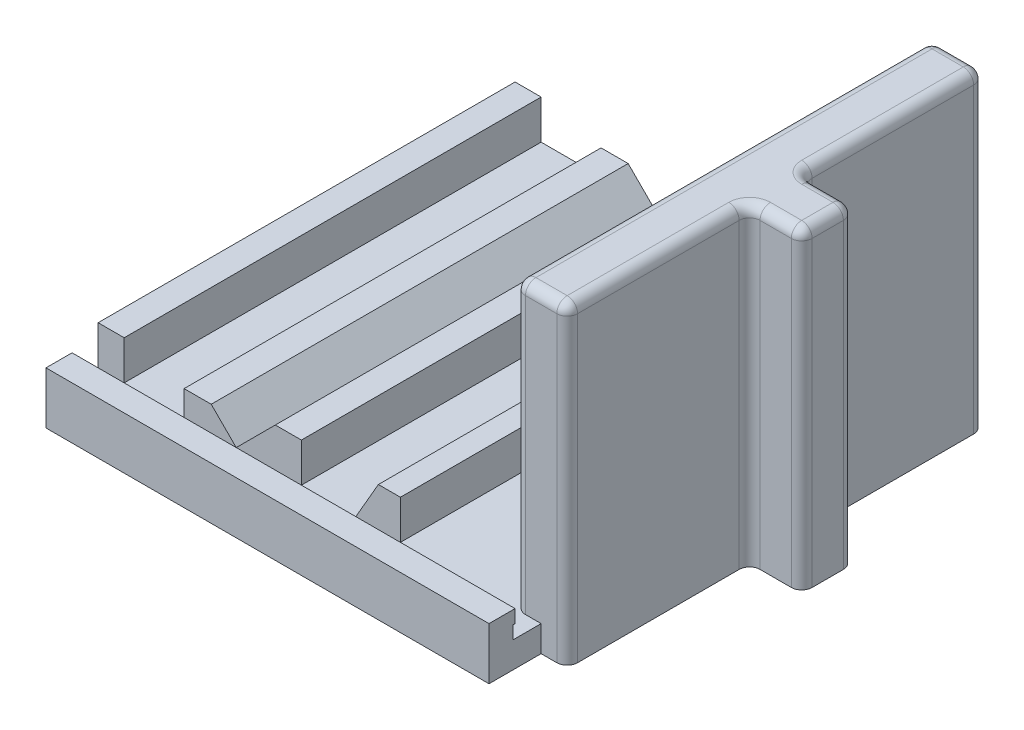
SolidWorks part; units mm, degrees
ref_plane "Front Plane" through (0, 0, 0) normal (0, 0, 1) x (1, 0, 0)
ref_plane "Top Plane" through (0, 0, 0) normal (0, 1, 0) x (1, 0, 0)
ref_plane "Right Plane" through (0, 0, 0) normal (1, 0, 0) x (0, 0, -1)
sketch "Sketch1" plane through (0, 0, 0) normal (0, 1, 0) x (1, 0, 0)
  line L0 (-25.4, 203.2) -> (-25.4, 0)
  line L1 (0, 0) -> (-25.4, 0)
  line L2 (0, 0) -> (0, 203.2)
  line L3 (0, 203.2) -> (-25.4, 203.2)
  line L4 (-25.4, 0) -> (-25.4, 203.2)
  line L5 (-25.4, 203.2) -> (-228.6, 203.2)
  line L6 (-25.4, 0) -> (-228.6, 0)
  line L7 (-228.6, 203.2) -> (-228.6, 0)
  line L8 (0, 101.6) -> (-228.6, 101.6) construction
  line L9 (0, 101.6) -> (104.3179, 101.6)
  line L10 (0, 114.3) -> (0, 88.9)
  line L13 (0, 114.3) -> (25.4, 114.3)
  line L14 (0, 88.9) -> (25.4, 88.9)
  line L15 (25.4, 114.3) -> (25.4, 88.9)
  dimension "D1" = 25.4
  dimension "D2" = 203.2
  dimension "D3" = 88.9
  dimension "D4" = 88.9
  dimension "D5" = 203.2
  dimension "D6" = 25.4
  dimension "D7" = 0
extrude "Boss-Extrude1" add sketch "Sketch1" along normal blind 12.7 contours L8 L0 L5 L7 | L4 L8 L7 L6 region at (-127, 0, -152.4) region at (-127, 0, -50.8)
sketch "Sketch2" plane through (0, 0, 0) normal (0, 1, 0) x (1, 0, 0)
  line L0 (-25.4, 0) -> (-25.4, 203.2)
  line L1 (-25.4, 0) -> (0, 0)
  line L2 (-25.4, 203.2) -> (0, 203.2)
  line L3 (0, 0) -> (0, 203.2)
  dimension "D1" = 25.4
sketch "Sketch3" plane through (0, 0, 0) normal (0, 1, 0) x (1, 0, 0)
  line L0 (0, 88.9) -> (0, 114.3)
  line L1 (0, 88.9) -> (25.4, 88.9)
  line L2 (0, 114.3) -> (25.4, 114.3)
  line L3 (25.4, 88.9) -> (25.4, 114.3)
  line L4 (0, 0) -> (0, 203.2) construction
  line L5 (-25.4, 203.2) -> (-228.6, 203.2) construction
  line L6 (-25.4, 0) -> (-228.6, 0) construction
  dimension "D1" = 88.9
  dimension "D2" = 88.9
  dimension "1" = 25.4
extrude "Boss-Extrude2" add sketch "Sketch2" along normal blind 152.4
extrude "Boss-Extrude3" add sketch "Sketch3" along normal blind 152.4
fillet "Fillet1" radius 5.08 16 edges at (-25.4, 152.4, -101.6) (-12.7, 152.4, -203.2) (0, 152.4, -158.75) (12.7, 152.4, -114.3) (25.4, 152.4, -101.6) (12.7, 152.4, -88.9) (0, 152.4, -44.45) (-12.7, 152.4, 0) (-25.4, 82.55, -203.2) (0, 76.2, -203.2) (0, 76.2, -114.3) (25.4, 76.2, -114.3) (25.4, 76.2, -88.9) (-25.4, 82.55, 0) (0, 76.2, 0) (0, 76.2, -88.9)
sketch "Sketch4" plane through (0, 12.7, 0) normal (0, 1, 0) x (1, 0, 0)
  line L4 (-20.32, 203.2) -> (-228.6, 203.2) construction
  line L5 (-20.32, 0) -> (-228.6, 0) construction
  line L7 (-167.64, 203.2) -> (-167.64, 0)
  line L8 (-167.64, 203.2) -> (-129.54, 203.2)
  line L9 (-167.64, 0) -> (-129.54, 0)
  line L10 (-129.54, 203.2) -> (-129.54, 0)
  line L11 (-106.68, 203.2) -> (-106.68, 0)
  line L12 (-106.68, 203.2) -> (-81.28, 203.2)
  line L13 (-106.68, 0) -> (-81.28, 0)
  line L14 (-81.28, 203.2) -> (-81.28, 0)
  line L15 (-228.6, 203.2) -> (-228.6, 0)
  line L16 (-228.6, 203.2) -> (-215.9, 203.2)
  line L17 (-228.6, 0) -> (-215.9, 0)
  line L18 (-215.9, 203.2) -> (-215.9, 0)
  line L19 (-25.4, 198.12) -> (-25.4, 5.08) construction
  dimension "D3" = 55.88
  dimension "D4" = 38.1
  dimension "D5" = 104.14
  dimension "D6" = 25.4
  dimension "D7" = 12.7
extrude "Boss-Extrude4" add sketch "Sketch4" along normal blind 19.05
chamfer "Chamfer1" distance 25.4 angle 45 1 edges at (-167.64, 31.75, -101.6)
chamfer "Chamfer2" distance 25.4 angle 30 1 edges at (-106.68, 31.75, -101.6) first distance on face at (-106.68, 22.225, -101.6)
sketch "Sketch6" plane through (0, 0, 0) normal (0, 1, 0) x (1, 0, 0)
  line L0 (-228.6, 0) -> (-12.7, 0)
  line L1 (-228.6, 0) -> (-228.6, -25.4)
  line L2 (-12.7, 0) -> (-12.7, -25.4)
  line L3 (-228.6, -25.4) -> (-12.7, -25.4)
  line L4 (-20.32, 0) -> (-81.28, 0) construction
  dimension "D1" = 25.4
  dimension "D2" = 215.9
sketch "Sketch7" plane through (0, 0, 0) normal (0, 0, 1) x (1, 0, 0)
  line L0 (-103.0138, 12.7) -> (-92.0153, 31.75)
  line L1 (-92.0153, 31.75) -> (19.7826, 225.3896)
  line L2 (-161.29, 12.7) -> (-142.24, 31.75)
  line L3 (-142.24, 31.75) -> (6.7651, 180.7551)
extrude "Boss-Extrude6" add sketch "Sketch6" along normal blind 12.7
sketch "Sketch8" plane through (0, 12.7, 0) normal (0, 1, 0) x (1, 0, 0)
  line L0 (-228.6, -25.4) -> (-12.7, -25.4)
  line L1 (-228.6, -25.4) -> (-228.6, -12.7)
  line L2 (-12.7, -25.4) -> (-12.7, -12.7)
  line L3 (-228.6, -12.7) -> (-12.7, -12.7)
  dimension "D1" = 12.7
extrude "Boss-Extrude7" add sketch "Sketch8" along normal blind 12.7
sketch "Sketch9" plane through (0, 0, 12.7) normal (0, 0, -1) x (-1, 0, 0)
  line L0 (228.6, 12.7) -> (12.7, 12.7)
  line L1 (228.6, 12.7) -> (228.6, 19.05)
  line L2 (12.7, 12.7) -> (12.7, 19.05)
  line L3 (228.6, 19.05) -> (12.7, 19.05)
  dimension "D1" = 6.35
extrude "Cut-Extrude1" cut sketch "Sketch9" against normal blind 0.9
sketch "Sketch10" plane through (0, 12.7, 0) normal (0, 1, 0) x (1, 0, 0)
  line L0 (-161.29, 203.2) -> (-161.29, 0)
  line L1 (-161.29, 203.2) -> (-186.69, 203.2)
  line L2 (-161.29, 0) -> (-186.69, 0)
  line L3 (-186.69, 203.2) -> (-186.69, 0)
  dimension "D1" = 25.4
extrude "Boss-Extrude8" add sketch "Sketch10" along normal blind 12.192
chamfer "Chamfer3" distance 12.192 angle 45 1 edges at (-161.29, 24.892, -101.6)
